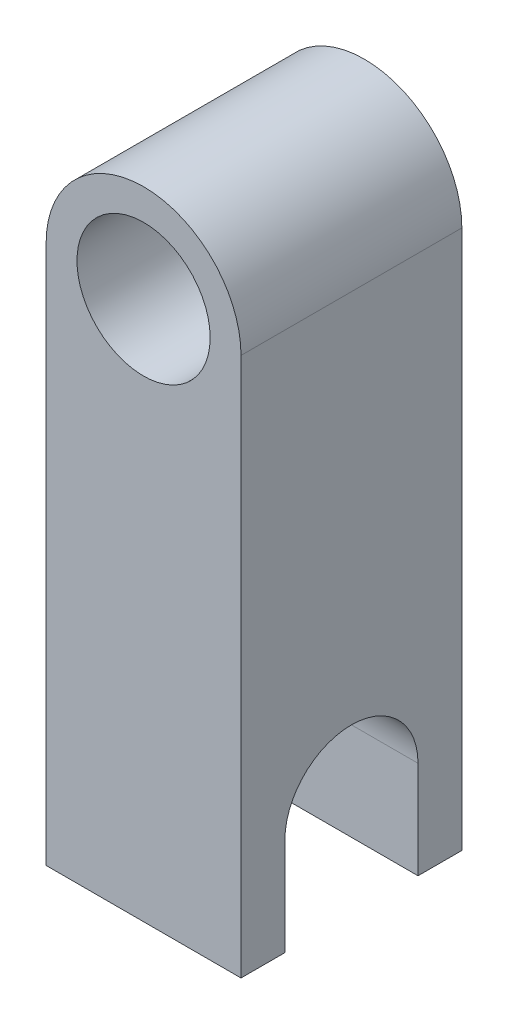
SolidWorks part; units mm, degrees
ref_plane "Front Plane" through (0, 0, 0) normal (0, 0, 1) x (1, 0, 0)
ref_plane "Top Plane" through (0, 0, 0) normal (0, 1, 0) x (1, 0, 0)
ref_plane "Right Plane" through (0, 0, 0) normal (1, 0, 0) x (0, 0, -1)
sketch "Sketch1" plane through (0, 0, 0) normal (0, 0, 1) x (1, 0, 0)
  line L0 (0, 0) -> (0, -68) construction
  line L1 (10.25, 0) -> (10.25, -68)
  line L2 (-10.25, 0) -> (-10.25, -68)
  line L3 (0, 0) -> (0, -68) construction
  line L4 (15, 0) -> (15, -68)
  line L5 (-15, 0) -> (-15, -68)
  arc A0 (10.25, 0) -> (-10.25, 0) centre (0, 0) ccw
  arc A1 (-10.25, -68) -> (10.25, -68) centre (0, -68) ccw
  arc A2 (15, 0) -> (-15, 0) centre (0, 0) ccw
  arc A3 (-15, -68) -> (15, -68) centre (0, -68) ccw
  circle A4 centre (0, 0) radius 10.25
  circle A5 centre (0, -68) radius 10.25
  point P3 (0, -34)
  point P10 (0, -34)
  dimension "D2" = 10.25
  dimension "D3" = 15
  dimension "D1" = 68
extrude "Boss-Extrude1" add sketch "Sketch1" along normal blind 34 contours L5 A3 L4 A2 A1 L2 A0 L1 | A5 L1 A4 L2 | A1 A5 region at (0, -34, 0) region at (0, -68, 0) region at (13.9751, -34, 0)
sketch "Sketch2" plane through (-15, 0, 0) normal (-1, 0, 0) x (0, 0, 1)
  line L1 (34, -83) -> (0, -83)
  line L2 (34, -83) -> (34, -68)
  line L3 (34, -68) -> (0, -68)
  line L4 (0, -83) -> (0, -68)
extrude "Boss-Extrude2" add sketch "Sketch2" against normal blind 30
sketch "Sketch3" plane through (-15, 0, 0) normal (-1, 0, 0) x (0, 0, 1)
  line L0 (17, 0) -> (17, -68) construction
  line L1 (34, 0) -> (0, 0) construction
  circle A0 centre (17, -68) radius 10.25
  dimension "D1" = 68
extrude "Cut-Extrude1" cut sketch "Sketch3" against normal blind 30
sketch "Sketch4" plane through (-15, 0, 0) normal (-1, 0, 0) x (0, 0, 1)
  line L0 (0, -83) -> (34, -83) construction
  line L1 (6.75, -68) -> (27.25, -68)
  line L2 (6.75, -68) -> (6.75, -83)
  line L3 (6.75, -83) -> (27.25, -83)
  line L4 (27.25, -68) -> (27.25, -83)
  circle A0 centre (17, -68) radius 10.25 construction
extrude "Cut-Extrude2" cut sketch "Sketch4" against normal blind 34
